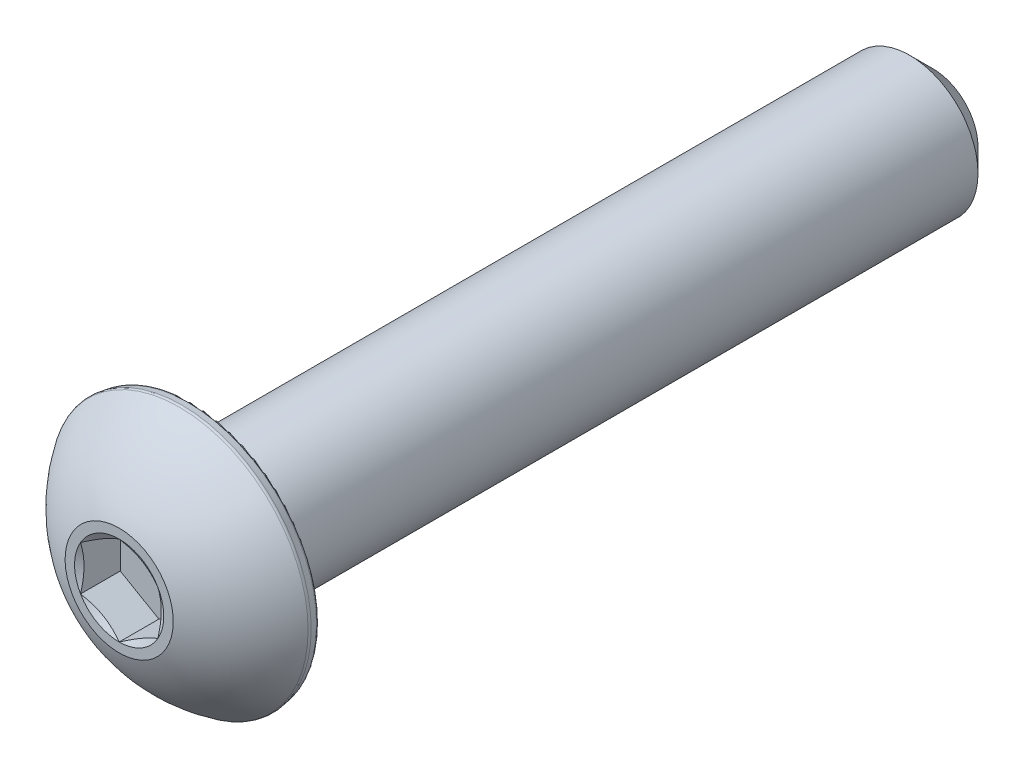
SolidWorks part; units mm, degrees
ref_plane "Front Plane" through (0, 0, 0) normal (0, 0, 1) x (1, 0, 0)
ref_plane "Top Plane" through (0, 0, 0) normal (0, 1, 0) x (1, 0, 0)
ref_plane "Right Plane" through (0, 0, 0) normal (1, 0, 0) x (0, 0, -1)
sketch "Sketch1" plane through (0, 0, 0) normal (1, 0, 0) x (0, 0, -1)
  line L0 (-10.4521, 0) -> (10.4521, 0) construction
  line L1 (-10.4521, 0) -> (-10.4521, 3.3274)
  line L2 (-10.4521, 3.3274) -> (-8.5979, 3.3274)
  line L3 (-8.5979, 3.3274) -> (-8.5979, 1.7526)
  line L4 (-8.5979, 1.7526) -> (10.4521, 1.7526)
  line L5 (10.4521, 1.7526) -> (10.4521, 0)
  point P2 (0, 0)
  point P4 (9.6584, 0)
  point P9 (9.2615, 1.7526)
  point P10 (9.2615, -1.7526)
  point P11 (10.4521, -1.7526)
  point P15 (-9.4323, 0)
  dimension "Head Height" = 1.8542
  dimension "Head Diameter" = 6.6548
  dimension "Length" = 19.05
  dimension "Screw Size Decimal Equivalent" = 3.5052
  dimension "Thread Pitch" = 0.7937
  dimension "D1" = 1.1906
  dimension "D2" = 1.0198
sketch "Sketch2" plane through (0, 0, 0) normal (0, 0, 1) x (1, 0, 0)
  line L0 (0, 1.7526) -> (0, 0) construction
  line L1 (0, 1.1457) -> (-0.9922, 0.5728)
  line L2 (-0.9922, 0.5728) -> (-0.9922, -0.5728)
  line L3 (-0.9922, -0.5728) -> (0, -1.1457)
  line L4 (0, -1.1457) -> (0.9922, -0.5728)
  line L5 (0.9922, -0.5728) -> (0.9922, 0.5728)
  line L6 (0.9922, 0.5728) -> (0, 1.1457)
  circle A0 centre (0, 0) radius 0.9922 construction
  circle A1 centre (0, 0) radius 1.3891
  point P10 (0, 1.3891)
  dimension "D1" = 2.7781
  dimension "Drive Size" = 1.9844
sketch "Sketch3" plane through (0, 0, 0) normal (1, 0, 0) x (0, 0, -1)
  line L0 (-10.4521, 0) -> (-10.4521, 1.3891)
  line L1 (-10.4521, 0) -> (-10.4521, 3.3274) construction
  line L2 (-10.4521, 3.3274) -> (-8.5979, 3.3274) construction
  line L3 (-8.876, 3.3274) -> (-8.5979, 3.2784)
  line L4 (-8.5979, 3.3274) -> (-8.5979, 1.7526) construction
  line L5 (-8.5979, 3.2784) -> (-8.5979, 1.7526)
  line L6 (-10.4521, 0) -> (10.4521, 0) construction
  line L7 (-10.4521, 0) -> (10.4521, 0)
  line L8 (10.4521, 0) -> (10.4521, 1.1573)
  line L9 (10.4521, 1.7526) -> (10.4521, 0) construction
  line L10 (10.4521, 1.1573) -> (9.8568, 1.7526)
  line L11 (-8.5979, 1.7526) -> (10.4521, 1.7526) construction
  line L12 (9.8568, 1.7526) -> (-8.5979, 1.7526)
  arc A0 (-10.4521, 1.3891) -> (-8.876, 3.3274) centre (-6.7638, 0) cw
  dimension "D1" = 0.2781
  dimension "D2" = 10
  dimension "D3" = 45
  dimension "D4" = 0.5953
revolve "Revolve1" add sketch "Sketch3" angle 360 about L7
sketch "Sketch4" plane through (0, 0, 10.4521) normal (0, 0, 1) x (1, 0, 0)
  line L0 (-0.9922, -0.5728) -> (0, -1.1457) construction
  line L1 (-0.9922, 0.5728) -> (-0.9922, -0.5728) construction
  line L2 (0, 1.1457) -> (-0.9922, 0.5728) construction
  line L3 (0.9922, 0.5728) -> (0, 1.1457) construction
  line L4 (0.9922, -0.5728) -> (0.9922, 0.5728) construction
  line L5 (0, -1.1457) -> (0.9922, -0.5728) construction
  line L6 (-0.9922, -0.5728) -> (0, -1.1457)
  line L7 (-0.9922, 0.5728) -> (-0.9922, -0.5728)
  line L8 (0, 1.1457) -> (-0.9922, 0.5728)
  line L9 (0.9922, 0.5728) -> (0, 1.1457)
  line L10 (0.9922, -0.5728) -> (0.9922, 0.5728)
  line L11 (0, -1.1457) -> (0.9922, -0.5728)
extrude "Cut-Extrude1" cut sketch "Sketch4" against normal up to vertex (1.0198 mm away) up to point (0, 0, 9.4323)
sketch "Sketch5" plane through (0, 0, 10.4521) normal (0, 0, 1) x (1, 0, 0)
  circle A0 centre (0, 0) radius 1.1457
extrude "Cut-Extrude2" cut sketch "Sketch5" against normal up to vertex (1.0198 mm away) draft 60 up to point (0, 0, 9.4323)
fillet "Fillet1" radius 0.0927 2 edges at (3.3274, 0, 8.876) (3.2784, 0, 8.5979)
split "Split1" [suppressed] bodies to split 106
sketch "Sketch6" [suppressed] plane through (0, 0, -10.4521) normal (0, 0, -1) x (-1, 0, 0)
  circle A0 centre (0, 0) radius 1.7526 construction
  circle A1 centre (0, 0) radius 1.7526
curve "Helix/Spiral1" [suppressed] pitch 0.7937 height 19.8438 turns 25
sketch "Sketch7" [suppressed] plane through (0, 0, 0) normal (1, 0, 0) x (0, 0, -1)
  line L0 (10.4025, 1.8385) -> (10.7994, 1.1511) construction
  line L1 (10.7994, 1.1511) -> (11.1962, 1.8385) construction
  line L2 (11.1962, 1.8385) -> (10.4025, 1.8385) construction
  line L3 (10.4273, 1.7956) -> (11.1714, 1.7956)
  line L4 (11.1714, 1.7956) -> (10.849, 1.237)
  line L5 (10.849, 1.237) -> (10.7498, 1.237)
  line L6 (10.7498, 1.237) -> (10.4273, 1.7956)
  line L7 (10.7994, 1.237) -> (10.7994, 1.1511) construction
  line L8 (10.4521, 1.7526) -> (11.1466, 1.7526) construction
  line L9 (10.7994, 1.8385) -> (10.7994, 1.7526) construction
  point P12 (10.7994, 1.7956)
  dimension "D1" = 0.7937
  dimension "D2" = 0.0992
sweep "Cut-Sweep1" [suppressed] cut profiles "Sketch7" path "Helix/Spiral1"
sketch "Sketch8" [suppressed] plane through (0, 0, 8.5979) normal (0, 0, -1) x (-1, 0, 0)
  circle A0 centre (0, 0) radius 1.8385
extrude "Boss-Extrude1" [suppressed] add sketch "Sketch8" along normal up to vertex draft 45
equation "\"D1@Sketch1\"=\"Thread Pitch@Sketch1\"*1.5"
equation "\"D2@Sketch1\"=0.55*\"Head Height@Sketch1\""
equation "\"D1@Sketch2\"=\"Drive Size@Sketch2\"*1.4"
equation "\"D1@Sketch3\"=0.15*\"Head Height@Sketch1\""
equation "\"D4@Sketch3\"=0.75*\"Thread Pitch@Sketch1\""
equation "\"D1@Fillet1\"=.05*\"Head Height@Sketch1\""
equation "\"D4@Helix/Spiral1\"=\"Thread Pitch@Sketch1\""
equation "\"D3@Helix/Spiral1\"=\"Length@Sketch1\"+\"Thread Pitch@Sketch1\""
equation "\"D2@Sketch7\"=\"D1@Sketch7\"/8"
equation "\"D1@Sketch7\"=\"Thread Pitch@Sketch1\""
